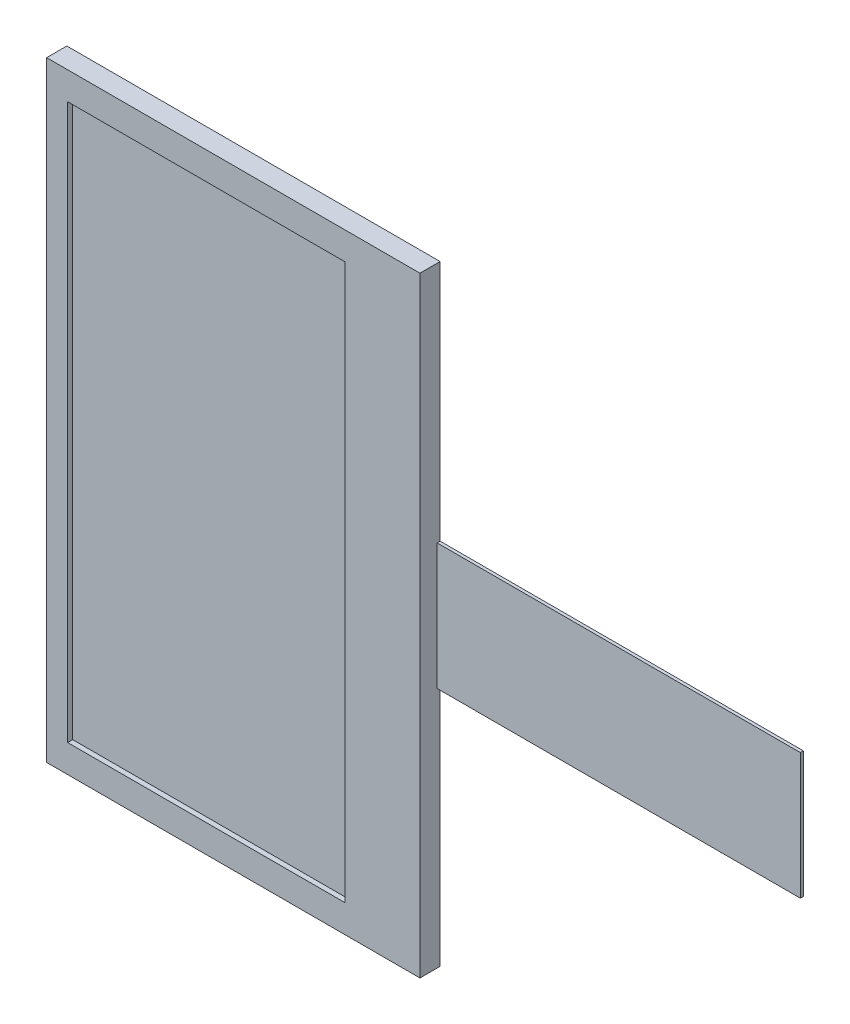
SolidWorks part; units mm, degrees
ref_plane "Front Plane" through (0, 0, 0) normal (0, 0, 1) x (1, 0, 0)
ref_plane "Top Plane" through (0, 0, 0) normal (0, 1, 0) x (1, 0, 0)
ref_plane "Right Plane" through (0, 0, 0) normal (1, 0, 0) x (0, 0, -1)
sketch "Sketch1" plane through (0, 0, 0) normal (0, 0, 1) x (1, 0, 0)
  line L1 (13.745, 27.505) -> (-13.745, 27.505)
  line L2 (13.745, 27.505) -> (13.745, -27.505)
  line L3 (13.745, -27.505) -> (-13.745, -27.505)
  line L4 (-13.745, 27.505) -> (-13.745, -27.505)
  line L5 (0, -27.505) -> (0, 27.505) construction
  line L6 (13.745, 0) -> (-13.745, 0) construction
  line L7 (21.175, 30.245) -> (-15.825, 30.245)
  line L8 (21.175, 30.245) -> (21.175, -30.255)
  line L9 (21.175, -30.255) -> (-15.825, -30.255)
  line L10 (-15.825, 30.245) -> (-15.825, -30.255)
  line L11 (2.675, -30.255) -> (2.675, 30.245) construction
  line L12 (21.175, -0.005) -> (-15.825, -0.005) construction
  line L13 (21.175, 6.245) -> (57.175, 6.245)
  line L15 (21.175, -6.255) -> (57.175, -6.255)
  line L16 (57.175, 6.245) -> (57.175, -6.255)
  line L17 (39.175, -6.255) -> (39.175, 6.245) construction
  line L18 (21.175, -0.005) -> (57.175, -0.005) construction
  point P0 (0, 0)
  point P4 (2.675, -0.005)
  point P8 (39.175, -0.005)
  point P12 (38.3185, -0.005)
  point P13 (23.3652, -7.7596)
  point P14 (27.5358, -6.255)
  point P15 (21.175, -6.255)
  point P16 (21.8393, -0.005)
  dimension "D1" = 27.49
  dimension "D2" = 37
  dimension "D3" = 55.01
  dimension "D4" = 60.5
  dimension "D5" = 12.5
  dimension "D6" = 36
  dimension "D7" = 2.08
  dimension "D8" = 2.75
extrude "Boss-Extrude1" add sketch "Sketch1" along normal blind 1.5 contours L1 L4 L3 L2 region at (0, 0, 0)
extrude "Boss-Extrude2" add sketch "Sketch1<3>" along normal blind 2 separate body contours L7 L10 L9 L8 L4 L1 L2 L3 region at (20.4658, 18.245, 0)
sketch "Sketch1<3>" plane through (0, 0, 0) normal (0, 0, 1) x (1, 0, 0) same geometry as "Sketch1"
extrude "Boss-Extrude3" add sketch "Sketch1<4>" along normal blind 0.3 separate body contours L9 L15 region at (39.175, -0.005, 0)
sketch "Sketch1<4>" plane through (0, 0, 0) normal (0, 0, 1) x (1, 0, 0) same geometry as "Sketch1"
